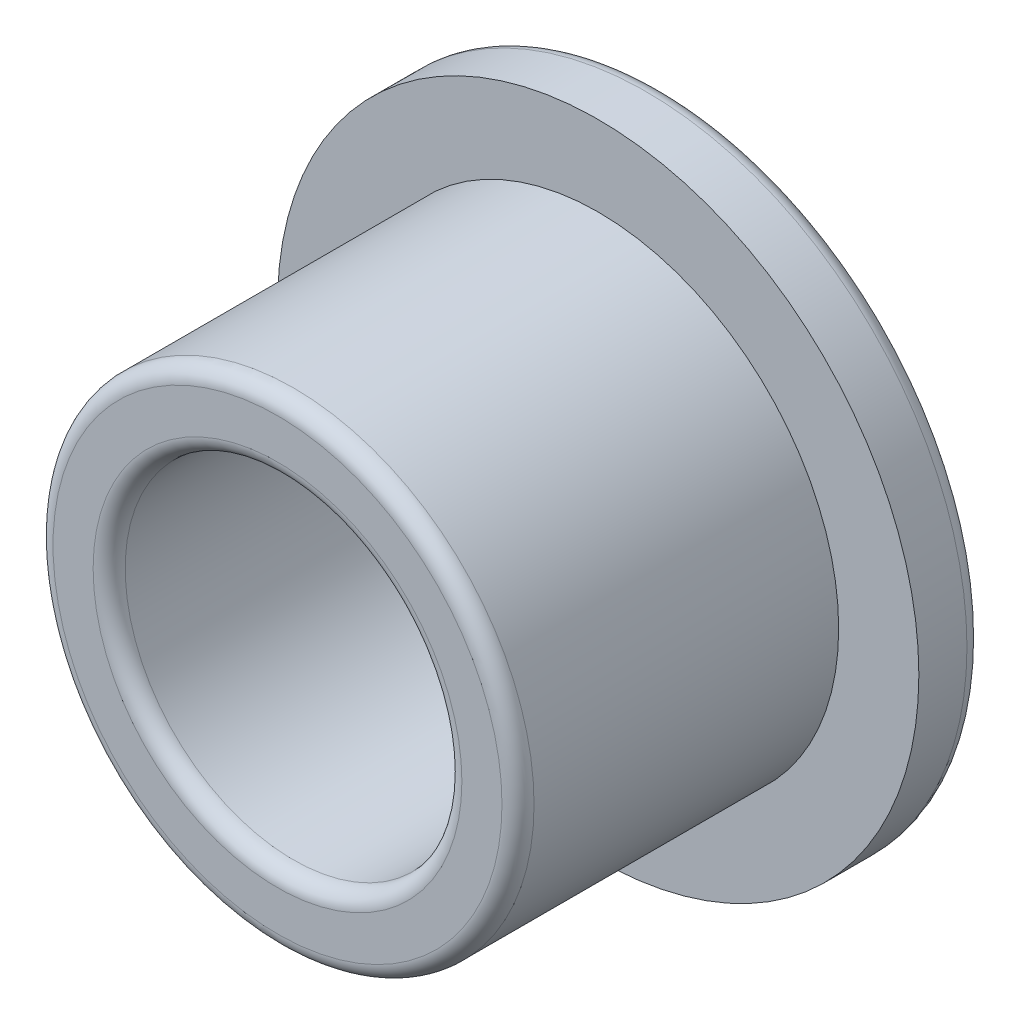
SolidWorks part; units mm, degrees
ref_plane "Přední rovina" through (0, 0, 0) normal (0, 0, 1) x (1, 0, 0)
ref_plane "Horní rovina" through (0, 0, 0) normal (0, 1, 0) x (1, 0, 0)
ref_plane "Pravá rovina" through (0, 0, 0) normal (1, 0, 0) x (0, 0, -1)
sketch "Skica1" plane through (0, 0, 0) normal (0, 0, 1) x (1, 0, 0)
  circle A0 centre (0, 0) radius 7.5
  circle A1 centre (0, 0) radius 5.25
  circle A2 centre (0, 0) radius 10
  dimension "D1" = 10.5
  dimension "D2" = 15
  dimension "D3" = 20
extrude "Přidat vysunutím1" add sketch "Skica1" along normal blind 10 contours A0 A1 region at (-7.2879, 0, 0)
extrude "Přidat vysunutím2" add sketch "Skica1<3>" against normal blind 2 contours A2 A0 | A0 A1 region at (-7.2879, 0, 0) region at (-9.7172, 0, 0)
sketch "Skica1<3>" plane through (0, 0, 0) normal (0, 0, 1) x (1, 0, 0) same geometry as "Skica1"
fillet "Zaoblit1" radius 0.5 4 edges at (7.5, 0, 10) (5.25, 0, 10) (5.25, 0, -2) (10, 0, -2)
